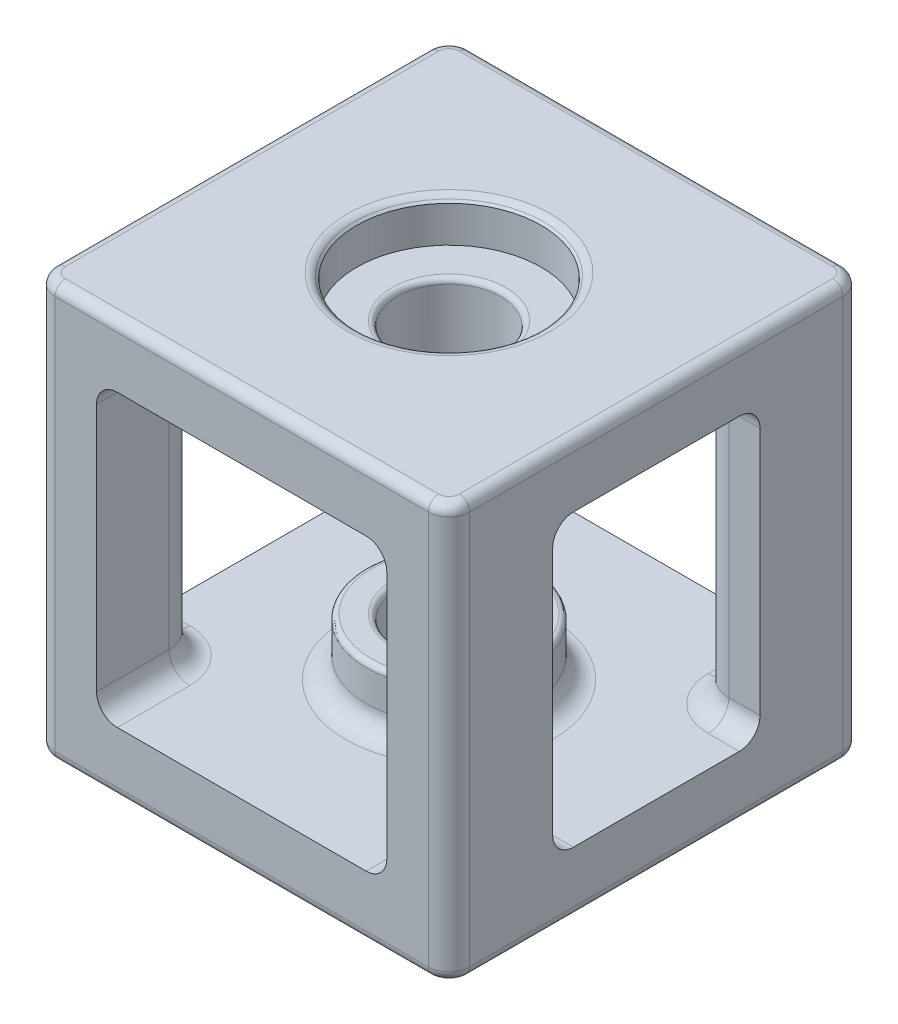
SolidWorks part; units mm, degrees
ref_plane "Front Plane" through (0, 0, 0) normal (0, 0, 1) x (1, 0, 0)
ref_plane "Top Plane" through (0, 0, 0) normal (0, 1, 0) x (1, 0, 0)
ref_plane "Right Plane" through (0, 0, 0) normal (1, 0, 0) x (0, 0, -1)
sketch "Sketch1" plane through (0, 0, 0) normal (0, 1, 0) x (1, 0, 0)
  line L0 (10, 5) -> (10, 10)
  line L1 (-10, 10) -> (10, 10)
  line L2 (-10, 10) -> (-10, -10)
  line L3 (-10, -10) -> (10, -10)
  line L4 (10, 10) -> (10, -10)
  line L5 (-10, 10) -> (10, -10) construction
  line L6 (-10, -10) -> (10, 10) construction
  line L7 (-7, 5) -> (-10, 5)
  line L8 (-7, 5) -> (-7, 10)
  line L9 (-7, 10) -> (-10, 10)
  line L10 (-10, 5) -> (-10, 10)
  line L11 (-7, 5) -> (-10, 10) construction
  line L12 (-7, 10) -> (-10, 5) construction
  line L13 (10, 5) -> (7, 5)
  line L14 (7, 5) -> (7, 10)
  line L15 (10, 10) -> (7, 10)
  line L16 (10, -10) -> (10, -5)
  line L17 (10, -10) -> (7, -10)
  line L18 (7, -10) -> (7, -5)
  line L19 (10, -5) -> (7, -5)
  line L20 (-7, -10) -> (-7, -5)
  line L21 (-7, -10) -> (-10, -10)
  line L22 (-10, -10) -> (-10, -5)
  line L23 (-7, -5) -> (-10, -5)
  circle A0 centre (0, 0) radius 4
  point P0 (0, 0)
  point P8 (-8.5, 7.5)
  point P9 (0, 0)
  point P13 (0, 0)
  dimension "D3" = 8
  dimension "D1" = 20
  dimension "D2" = 20
  dimension "D4" = 3
  dimension "D5" = 5
  dimension "D6" = 2
  dimension "D7" = 2
extrude "Boss-Extrude1" add sketch "Sketch1" along normal blind 3 contours L2 L3 L4 L1
extrude "Boss-Extrude2" add sketch "Sketch1<3>" along normal blind 5.75 contours A0
sketch "Sketch1<3>" plane through (0, 0, 0) normal (0, 1, 0) x (1, 0, 0) same geometry as "Sketch1"
sketch "Sketch2" plane through (0, 5.75, 0) normal (0, 1, 0) x (1, 0, 0)
  circle A0 centre (0, 0) radius 2.5
  dimension "D1" = 5
extrude "Cut-Extrude1" cut sketch "Sketch2" against normal up to surface (5.75 mm away) up to face at (0, 0, 0)
ref_plane "Plane1" through (0, 10, 0) normal (0, 1, 0) x (1, 0, 0)
extrude "Boss-Extrude3" add sketch "Sketch1<4>" along normal blind 20 contours L9 L8 L7 L10 | L13 L14 L15 L0 | L19 L18 L17 L16 | L23 L22 L21 L20
sketch "Sketch1<4>" plane through (0, 0, 0) normal (0, 1, 0) x (1, 0, 0) same geometry as "Sketch1"
mirror "Mirror2" about plane through (0, 10, 0) normal (0, 1, 0) of "Cut-Extrude1", "Boss-Extrude1", "Boss-Extrude2"
fillet "Fillet1" radius 1 4 edges at (-10, 10, -10) (10, 10, -10) (10, 10, 10) (-10, 10, 10)
fillet "Fillet2" radius 1.5 4 edges at (-7, 10, 5) (7, 10, 5) (7, 10, -5) (-7, 10, -5)
fillet "Fillet5" radius 1 26 edges at (-9.25, 3, 5) (-7.4393, 3, 5.4393) (-9.25, 3, -5) (-7.4393, 3, -5.4393) (7, 3, 8.25) (7.4393, 3, 5.4393) (9.25, 3, -5) (7.4393, 3, -5.4393) (0, 3, -4) (-7, 3, 8.25) (-7, 3, -8.25) (9.25, 3, 5) (7, 3, -8.25) (9.25, 17, 5) (7.4393, 17, 5.4393) (-9.25, 17, 5) (-7.4393, 17, 5.4393) (-7, 17, -8.25) (-7.4393, 17, -5.4393) (7, 17, -8.25) (7.4393, 17, -5.4393) (7, 17, 8.25) (-7, 17, 8.25) (-9.25, 17, -5) (0, 17, 4) (9.25, 17, -5)
sketch "Sketch5" plane through (0, 20, 0) normal (0, 1, 0) x (1, 0, 0)
  circle A0 centre (0, 0) radius 4.45
  dimension "D1" = 8.9
extrude "Cut-Extrude2" cut sketch "Sketch5" against normal blind 2
chamfer "Chamfer1" distance 0.25 angle 45 1 edges at (0, 20, 4.45)
fillet "Fillet6" radius 0.5 18 edges at (0, 0, -2.5) (-9.7071, 0, 9.7071) (0, 0, 10) (9.7071, 0, 9.7071) (10, 0, 0) (9.7071, 0, -9.7071) (0, 0, -10) (-9.7071, 0, -9.7071) (-10, 0, 0) (9.7071, 20, -9.7071) (10, 20, 0) (9.7071, 20, 9.7071) (0, 20, 10) (-9.7071, 20, 9.7071) (-10, 20, 0) (-9.7071, 20, -9.7071) (0, 20, -10) (0, 20, 4.7)
fillet "Fillet7" radius 0.25 5 edges at (0, 5.75, 4) (0, 14.25, 4) (0, 14.25, 2.5) (0, 5.75, 2.5) (0, 18, 2.5)
